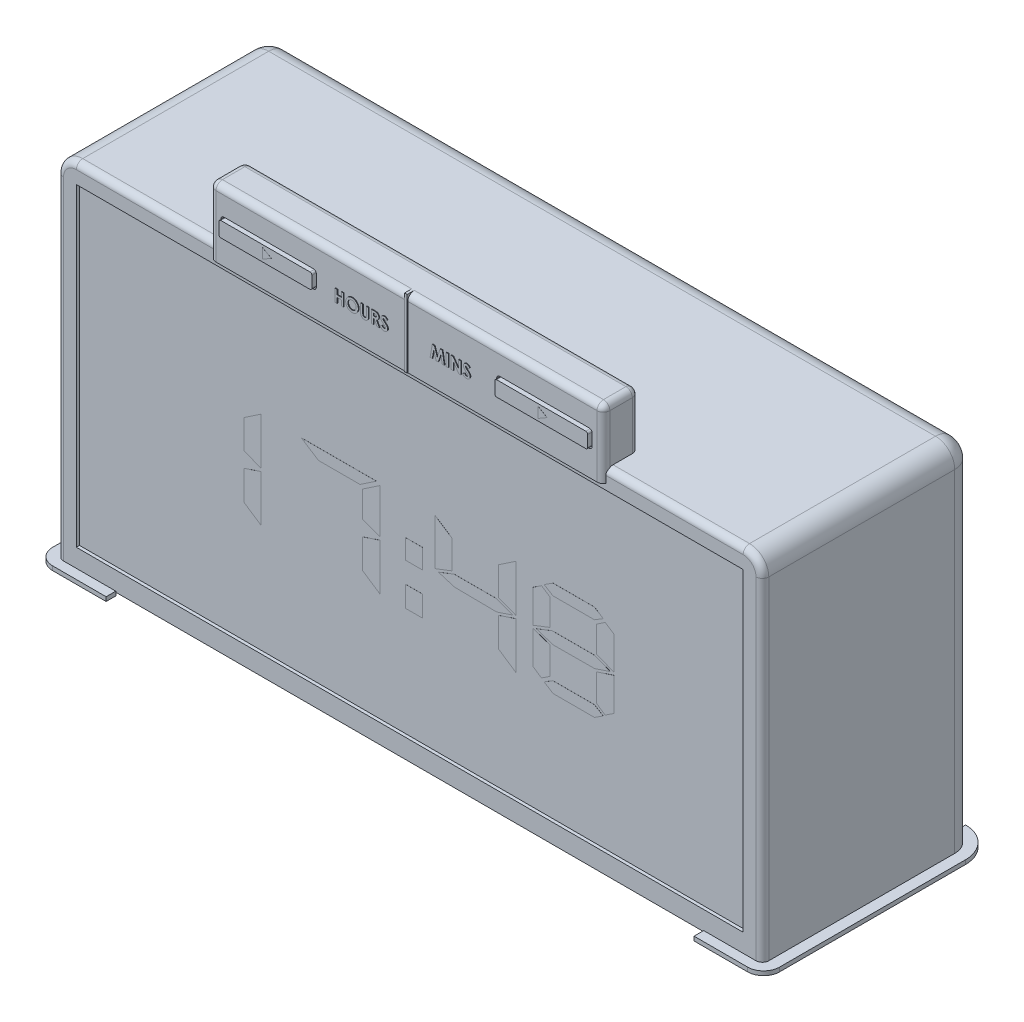
SolidWorks part; units mm, degrees
ref_plane "Front Plane" through (0, 0, 0) normal (0, 0, 1) x (1, 0, 0)
ref_plane "Top Plane" through (0, 0, 0) normal (0, 1, 0) x (1, 0, 0)
ref_plane "Right Plane" through (0, 0, 0) normal (1, 0, 0) x (0, 0, -1)
sketch "Sketch13" plane through (0, 0, 0) normal (0, 0, 1) x (1, 0, 0)
  line L1 (55, 27.5) -> (-55, 27.5)
  line L2 (55, 27.5) -> (55, -27.5)
  line L3 (55, -27.5) -> (-55, -27.5)
  line L4 (-55, 27.5) -> (-55, -27.5)
  line L5 (55, 27.5) -> (-55, -27.5) construction
  line L6 (55, -27.5) -> (-55, 27.5) construction
  point P0 (0, 0)
  dimension "D1" = 110
  dimension "D2" = 55
extrude "Boss-Extrude6" add sketch "Sketch13" along normal mid plane 33
sketch "Sketch14" plane through (0, 0, 16.5) normal (0, 0, 1) x (1, 0, 0)
  line L8 (-52, 24.5) -> (-52, -24.5)
  line L9 (-52, -24.5) -> (52, -24.5)
  line L10 (52, -24.5) -> (52, 24.5)
  line L11 (52, 24.5) -> (-52, 24.5)
  line L12 (-52, 24.5) -> (-52, -24.5)
  line L13 (-52, -24.5) -> (52, -24.5)
  line L14 (52, -24.5) -> (52, 24.5)
  line L15 (52, 24.5) -> (-52, 24.5)
  dimension "D1" = 3
extrude "Cut-Extrude7" cut sketch "Sketch14" against normal blind 0.5
sketch "Sketch15" plane through (0, -27.5, 0) normal (0, -1, 0) x (1, 0, 0)
  line L0 (-55, -16.5) -> (-56.6952, -16.5)
  line L1 (-56.6952, -16.5) -> (-56.6952, 18.0065)
  line L2 (-56.6952, 18.0065) -> (-45.8479, 18.0065)
  line L3 (-45.8479, 18.0065) -> (-45.8479, 16.5)
  line L4 (-55, 16.5) -> (55, 16.5) construction
  line L5 (-45.8479, 16.5) -> (-55, 16.5)
  line L6 (-55, 16.5) -> (-55, -16.5)
  line L8 (55, 16.5) -> (55, -16.5)
  line L9 (45.8479, 16.5) -> (55, 16.5)
  line L10 (45.8479, 18.0065) -> (45.8479, 16.5)
  line L11 (56.6952, 18.0065) -> (45.8479, 18.0065)
  line L12 (56.6952, -16.5) -> (56.6952, 18.0065)
  line L13 (55, -16.5) -> (56.6952, -16.5)
extrude "Boss-Extrude7" add sketch "Sketch15" along normal blind 0.5
sketch "Sketch16" plane through (0, 0, 16.5) normal (0, 0, 1) x (1, 0, 0)
  line L0 (52, 24.5) -> (-52, 24.5) construction
  line L1 (-30.7122, 36.053) -> (30.7122, 36.053)
  line L3 (30.7122, 36.053) -> (30.7122, 25.413)
  line L4 (30.7122, 25.413) -> (-30.7122, 25.413)
  line L5 (-30.7122, 36.053) -> (-30.7122, 25.413)
  point P0 (0, 24.5)
  point P1 (0, 29.913)
extrude "Boss-Extrude8" add sketch "Sketch16" along normal blind 0.5 and the other way blind 5
sketch "Sketch18" plane through (0, 0, 17) normal (0, 0, 1) x (1, 0, 0)
  line L1 (-14.5603, 31.9082) -> (-28.4603, 31.9082)
  line L2 (-14.2603, 31.6082) -> (-14.2603, 29.8579)
  line L3 (-14.5603, 29.5579) -> (-28.4603, 29.5579)
  line L4 (-28.7603, 31.6082) -> (-28.7603, 29.8579)
  line L5 (-14.2603, 31.9082) -> (-28.7603, 29.5579) construction
  line L6 (-14.2603, 29.5579) -> (-28.7603, 31.9082) construction
  line L7 (14.2603, 29.5579) -> (28.7603, 31.9082) construction
  line L8 (14.2603, 31.9082) -> (28.7603, 29.5579) construction
  line L9 (28.7603, 31.6082) -> (28.7603, 29.8579)
  line L10 (14.5603, 29.5579) -> (28.4603, 29.5579)
  line L11 (14.2603, 31.6082) -> (14.2603, 29.8579)
  line L12 (14.5603, 31.9082) -> (28.4603, 31.9082)
  arc A0 (28.4603, 29.5579) -> (28.7603, 29.8579) centre (28.4603, 29.8579) ccw
  arc A1 (28.4603, 31.9082) -> (28.7603, 31.6082) centre (28.4603, 31.6082) cw
  arc A2 (14.2603, 29.8579) -> (14.5603, 29.5579) centre (14.5603, 29.8579) ccw
  arc A3 (14.5603, 31.9082) -> (14.2603, 31.6082) centre (14.5603, 31.6082) ccw
  arc A4 (-14.2603, 29.8579) -> (-14.5603, 29.5579) centre (-14.5603, 29.8579) cw
  arc A5 (-14.5603, 31.9082) -> (-14.2603, 31.6082) centre (-14.5603, 31.6082) cw
  arc A6 (-28.4603, 29.5579) -> (-28.7603, 29.8579) centre (-28.4603, 29.8579) cw
  arc A7 (-28.4603, 31.9082) -> (-28.7603, 31.6082) centre (-28.4603, 31.6082) ccw
  point P0 (-21.5103, 30.733)
  point P12 (21.5103, 30.733)
  dimension "D2" = 0.3
  dimension "D1" = 14.5
extrude "Boss-Extrude9" add sketch "Sketch18" along normal blind 0.5
sketch "Sketch19" plane through (0, 0, 17) normal (0, 0, 1) x (1, 0, 0)
  line L0 (-14.2603, 29.8579) -> (-14.2603, 31.6082) construction
  line L1 (-14.5603, 31.9082) -> (-28.4603, 31.9082) construction
  line L2 (-28.7603, 31.6082) -> (-28.7603, 29.8579) construction
  line L3 (-28.4603, 29.5579) -> (-14.5603, 29.5579) construction
  line L4 (28.7603, 29.8579) -> (28.7603, 31.6082) construction
  line L5 (28.4603, 31.9082) -> (14.5603, 31.9082) construction
  line L6 (14.2603, 31.6082) -> (14.2603, 29.8579) construction
  line L7 (14.5603, 29.5579) -> (28.4603, 29.5579) construction
  line L8 (-14.2603, 29.8579) -> (-14.2603, 31.6082)
  line L9 (-14.5603, 31.9082) -> (-28.4603, 31.9082)
  line L10 (-28.7603, 31.6082) -> (-28.7603, 29.8579)
  line L11 (-28.4603, 29.5579) -> (-14.5603, 29.5579)
  line L12 (28.7603, 29.8579) -> (28.7603, 31.6082)
  line L13 (28.4603, 31.9082) -> (14.5603, 31.9082)
  line L14 (14.2603, 31.6082) -> (14.2603, 29.8579)
  line L15 (14.5603, 29.5579) -> (28.4603, 29.5579)
  line L16 (-14.5603, 32.1082) -> (-28.4603, 32.1082)
  line L17 (-28.9603, 31.6082) -> (-28.9603, 29.8579)
  line L18 (-28.4603, 29.3579) -> (-14.5603, 29.3579)
  line L19 (-14.0603, 29.8579) -> (-14.0603, 31.6082)
  line L20 (28.9603, 29.8579) -> (28.9603, 31.6082)
  line L21 (28.4603, 32.1082) -> (14.5603, 32.1082)
  line L22 (14.0603, 31.6082) -> (14.0603, 29.8579)
  line L23 (14.5603, 29.3579) -> (28.4603, 29.3579)
  arc A0 (-14.5603, 29.5579) -> (-14.2603, 29.8579) centre (-14.5603, 29.8579) ccw construction
  arc A1 (-14.2603, 31.6082) -> (-14.5603, 31.9082) centre (-14.5603, 31.6082) ccw construction
  arc A2 (-28.4603, 31.9082) -> (-28.7603, 31.6082) centre (-28.4603, 31.6082) ccw construction
  arc A3 (-28.7603, 29.8579) -> (-28.4603, 29.5579) centre (-28.4603, 29.8579) ccw construction
  arc A4 (28.4603, 29.5579) -> (28.7603, 29.8579) centre (28.4603, 29.8579) ccw construction
  arc A5 (28.7603, 31.6082) -> (28.4603, 31.9082) centre (28.4603, 31.6082) ccw construction
  arc A6 (14.5603, 31.9082) -> (14.2603, 31.6082) centre (14.5603, 31.6082) ccw construction
  arc A7 (14.2603, 29.8579) -> (14.5603, 29.5579) centre (14.5603, 29.8579) ccw construction
  arc A8 (-14.5603, 29.5579) -> (-14.2603, 29.8579) centre (-14.5603, 29.8579) ccw
  arc A9 (-14.2603, 31.6082) -> (-14.5603, 31.9082) centre (-14.5603, 31.6082) ccw
  arc A10 (-28.4603, 31.9082) -> (-28.7603, 31.6082) centre (-28.4603, 31.6082) ccw
  arc A11 (-28.7603, 29.8579) -> (-28.4603, 29.5579) centre (-28.4603, 29.8579) ccw
  arc A12 (28.4603, 29.5579) -> (28.7603, 29.8579) centre (28.4603, 29.8579) ccw
  arc A13 (28.7603, 31.6082) -> (28.4603, 31.9082) centre (28.4603, 31.6082) ccw
  arc A14 (14.5603, 31.9082) -> (14.2603, 31.6082) centre (14.5603, 31.6082) ccw
  arc A15 (14.2603, 29.8579) -> (14.5603, 29.5579) centre (14.5603, 29.8579) ccw
  arc A16 (-28.4603, 32.1082) -> (-28.9603, 31.6082) centre (-28.4603, 31.6082) ccw
  arc A17 (-28.9603, 29.8579) -> (-28.4603, 29.3579) centre (-28.4603, 29.8579) ccw
  arc A18 (-14.5603, 29.3579) -> (-14.0603, 29.8579) centre (-14.5603, 29.8579) ccw
  arc A19 (-14.0603, 31.6082) -> (-14.5603, 32.1082) centre (-14.5603, 31.6082) ccw
  arc A20 (28.9603, 31.6082) -> (28.4603, 32.1082) centre (28.4603, 31.6082) ccw
  arc A21 (14.5603, 32.1082) -> (14.0603, 31.6082) centre (14.5603, 31.6082) ccw
  arc A22 (14.0603, 29.8579) -> (14.5603, 29.3579) centre (14.5603, 29.8579) ccw
  arc A23 (28.4603, 29.3579) -> (28.9603, 29.8579) centre (28.4603, 29.8579) ccw
  dimension "D1" = 0.2
  dimension "D2" = 0.2
extrude "Cut-Extrude8" cut sketch "Sketch19" against normal blind 0.5
sketch "Sketch20" plane through (0, 0, 17) normal (0, 0, 1) x (1, 0, 0)
  line L0 (-0.2, 36.053) -> (0.2, 36.053)
  line L3 (-0.2, 36.053) -> (-0.2, 25.413)
  line L4 (0.2, 36.053) -> (0.2, 25.413)
  line L5 (-0.2, 25.413) -> (0.2, 25.413)
extrude "Boss-Extrude10" add sketch "Sketch20" along normal blind 0.1
sketch "Sketch21" plane through (0, 0, 17) normal (0, 0, 1) x (1, 0, 0)
  line L0 (-12.2293, 29.3579) -> (-1.6239, 29.3579) construction
  line L3 (12.2293, 29.3579) -> (1.6239, 29.3579) construction
  text T0 "<b>HOURS</b>" font "Century Gothic" height 1.9
  text T1 "<b>MINS</b>" font "Century Gothic" height 1.9
extrude "Boss-Extrude11" add sketch "Sketch21" along normal blind 0.1
sketch "Sketch22" plane through (0, 0, 17.5) normal (0, 0, 1) x (1, 0, 0)
  line L1 (-20.5865, 30.733) -> (-21.9722, 31.533)
  line L2 (-21.9722, 31.533) -> (-21.9722, 29.933)
  line L3 (-21.9722, 29.933) -> (-20.5865, 30.733)
  line L4 (22.4341, 30.733) -> (21.0484, 31.533)
  line L5 (21.0484, 31.533) -> (21.0484, 29.933)
  line L6 (21.0484, 29.933) -> (22.4341, 30.733)
  circle A0 centre (-21.5103, 30.733) radius 0.4619 construction
  circle A1 centre (21.5103, 30.733) radius 0.4619 construction
  dimension "D1" = 1.6
  dimension "D2" = 1.6
extrude "Boss-Extrude12" add sketch "Sketch22" along normal blind 0.01
fillet "Fillet14" radius 1 9 edges at (-30.7122, 31.7765, 11.5) (30.7122, 36.053, 14.25) (0, 36.053, 11.5) (30.7122, 31.7765, 11.5) (30.7122, 30.733, 17) (-30.7122, 30.733, 17) (-30.7122, 36.053, 14.25)
fillet "Fillet15" radius 3 5 edges at (55, 0, -16.5) (55, 27.5, 0) (0, 27.5, -16.5) (-55, 0, -16.5) (-55, 27.5, 0)
fillet "Fillet16" radius 1 6 edges at (55, -1.5, 16.5) (54.1213, 26.6213, 16.5) (-55, -1.5, 16.5) (-54.1213, 26.6213, 16.5) (41.2891, 27.5, 16.5) (-41.2891, 27.5, 16.5)
sketch "Sketch23" plane through (0, -27.5, 0) normal (0, 1, 0) x (1, 0, 0)
  line L0 (-55, 16.5) -> (-55, -16.5) construction
  line L1 (-55, -16.5) -> (-45.8479, -16.5) construction
  line L2 (-55, -15.5) -> (-55, -16.5)
  line L3 (-55, -16.5) -> (-54, -16.5)
  line L4 (-56.6952, -18.0065) -> (-56.6952, 16.5) construction
  line L5 (-52, 18.1952) -> (-52, 16.5)
  line L6 (-56.6952, 13.5) -> (-55, 13.5)
  line L8 (56.6952, 13.5) -> (55, 13.5)
  line L9 (52, 18.1952) -> (52, 16.5)
  line L10 (55, -16.5) -> (54, -16.5)
  line L11 (55, -15.5) -> (55, -16.5)
  arc A0 (-55, -15.5) -> (-54, -16.5) centre (-54, -15.5) ccw construction
  arc A1 (-55, -15.5) -> (-54, -16.5) centre (-54, -15.5) ccw
  arc A2 (-52, 16.5) -> (-55, 13.5) centre (-52, 13.5) ccw construction
  arc A3 (-52, 16.5) -> (-55, 13.5) centre (-52, 13.5) ccw
  arc A4 (-56.6952, 13.5) -> (-52, 18.1952) centre (-52, 13.5) cw
  arc A5 (56.6952, 13.5) -> (52, 18.1952) centre (52, 13.5) ccw
  arc A6 (52, 16.5) -> (55, 13.5) centre (52, 13.5) cw
  arc A7 (55, -15.5) -> (54, -16.5) centre (54, -15.5) cw
extrude "Boss-Extrude13" add sketch "Sketch23" against normal up to surface (0.5 mm away) up to face at (-52.5144, -28, 6.0022)
sketch "Sketch24" plane through (0, -27.5, 0) normal (0, 1, 0) x (1, 0, 0)
  line L0 (-56.6952, 16.5) -> (-55.6118, 16.5) construction
  line L1 (-56.6952, -18.0065) -> (-56.6952, 16.5) construction
  line L2 (-56.6952, 16.5) -> (-55.6118, 16.5)
  line L3 (-56.6952, 13.5) -> (-56.6952, 16.5)
  line L5 (56.6952, 13.5) -> (56.6952, 16.5)
  line L6 (56.6952, 16.5) -> (55.6118, 16.5)
  arc A0 (-52, 18.1952) -> (-56.6952, 13.5) centre (-52, 13.5) ccw construction
  arc A1 (-55.6118, 16.5) -> (-56.6952, 13.5) centre (-52, 13.5) ccw
  arc A2 (55.6118, 16.5) -> (56.6952, 13.5) centre (52, 13.5) cw
extrude "Cut-Extrude9" cut sketch "Sketch24" against normal blind 15.01
fillet "Fillet17" radius 2.5 1 edges at (-56.6952, -27.75, 18.0065)
fillet "Fillet18" radius 2.5 1 edges at (56.6952, -27.75, 18.0065)
sketch "Sketch25" plane through (0, -27.5, 0) normal (0, 1, 0) x (1, 0, 0)
  line L6 (-56.6952, 13.5) -> (-56.6952, -15.5065)
  line L7 (-54.1952, -18.0065) -> (-45.8479, -18.0065)
  line L8 (-45.8479, -18.0065) -> (-45.8479, -16.5)
  line L9 (-45.8479, -16.5) -> (-54, -16.5)
  line L10 (-55, -15.5) -> (-55, 13.5)
  line L11 (-52, 16.5) -> (-52, 18.1952)
  line L12 (-56.6952, 13.5) -> (-56.6952, -15.5065)
  line L13 (-54.1952, -18.0065) -> (-45.8479, -18.0065)
  line L14 (-45.8479, -18.0065) -> (-45.8479, -16.5)
  line L15 (-45.8479, -16.5) -> (-54, -16.5)
  line L16 (-55, -15.5) -> (-55, 13.5)
  line L17 (-52, 16.5) -> (-52, 18.1952)
  line L18 (45.8479, -18.0065) -> (54.1952, -18.0065)
  line L19 (56.6952, -15.5065) -> (56.6952, 13.5)
  line L20 (52, 18.1952) -> (52, 16.5)
  line L21 (55, 13.5) -> (55, -15.5)
  line L22 (54, -16.5) -> (45.8479, -16.5)
  line L23 (45.8479, -16.5) -> (45.8479, -18.0065)
  line L24 (45.8479, -18.0065) -> (54.1952, -18.0065)
  line L25 (56.6952, -15.5065) -> (56.6952, 13.5)
  line L26 (52, 18.1952) -> (52, 16.5)
  line L27 (55, 13.5) -> (55, -15.5)
  line L28 (54, -16.5) -> (45.8479, -16.5)
  line L29 (45.8479, -16.5) -> (45.8479, -18.0065)
  arc A4 (-56.6952, -15.5065) -> (-54.1952, -18.0065) centre (-54.1952, -15.5065) ccw
  arc A5 (-55, -15.5) -> (-54, -16.5) centre (-54, -15.5) ccw
  arc A6 (-52, 16.5) -> (-55, 13.5) centre (-52, 13.5) ccw
  arc A7 (-52, 18.1952) -> (-56.6952, 13.5) centre (-52, 13.5) ccw
  arc A8 (-56.6952, -15.5065) -> (-54.1952, -18.0065) centre (-54.1952, -15.5065) ccw
  arc A9 (-55, -15.5) -> (-54, -16.5) centre (-54, -15.5) ccw
  arc A10 (-52, 16.5) -> (-55, 13.5) centre (-52, 13.5) ccw
  arc A11 (-52, 18.1952) -> (-56.6952, 13.5) centre (-52, 13.5) ccw
  arc A12 (54.1952, -18.0065) -> (56.6952, -15.5065) centre (54.1952, -15.5065) ccw
  arc A13 (56.6952, 13.5) -> (52, 18.1952) centre (52, 13.5) ccw
  arc A14 (55, 13.5) -> (52, 16.5) centre (52, 13.5) ccw
  arc A15 (54, -16.5) -> (55, -15.5) centre (54, -15.5) ccw
  arc A16 (54.1952, -18.0065) -> (56.6952, -15.5065) centre (54.1952, -15.5065) ccw
  arc A17 (56.6952, 13.5) -> (52, 18.1952) centre (52, 13.5) ccw
  arc A18 (55, 13.5) -> (52, 16.5) centre (52, 13.5) ccw
  arc A19 (54, -16.5) -> (55, -15.5) centre (54, -15.5) ccw
  dimension "D1" = 0
  dimension "D2" = 0
extrude "Boss-Extrude14" add sketch "Sketch25" along normal blind 0.15
sketch "Sketch26" plane through (0, 0, -16.5) normal (0, 0, -1) x (-1, 0, 0)
  circle A0 centre (0, -22.1261) radius 2.1733
extrude "Cut-Extrude10" cut sketch "Sketch26" against normal blind 5.15
fillet "Fillet19" radius 0.5 1 edges at (-2.1733, -22.1261, -16.5)
sketch "Sketch27" plane through (0, 0, 16) normal (0, 0, 1) x (1, 0, 0)
  line L0 (34.5388, -7.5663) -> (-34.5388, -7.5663) construction
  text T0 "17:48" font "DigifaceWide" height 15
  point P3 (0, -7.5663)
extrude "Boss-Extrude15" add sketch "Sketch27" along normal blind 0.01
sketch "Sketch28" plane through (0, 0, -16.5) normal (0, 0, -1) x (-1, 0, 0)
  line L0 (31.2549, 21.2237) -> (50.987, 21.2237) construction
  text T0 "Karajko Mirzet" font "Freestyle Script" height 2
extrude "Boss-Extrude16" add sketch "Sketch28" along normal blind 0.1
